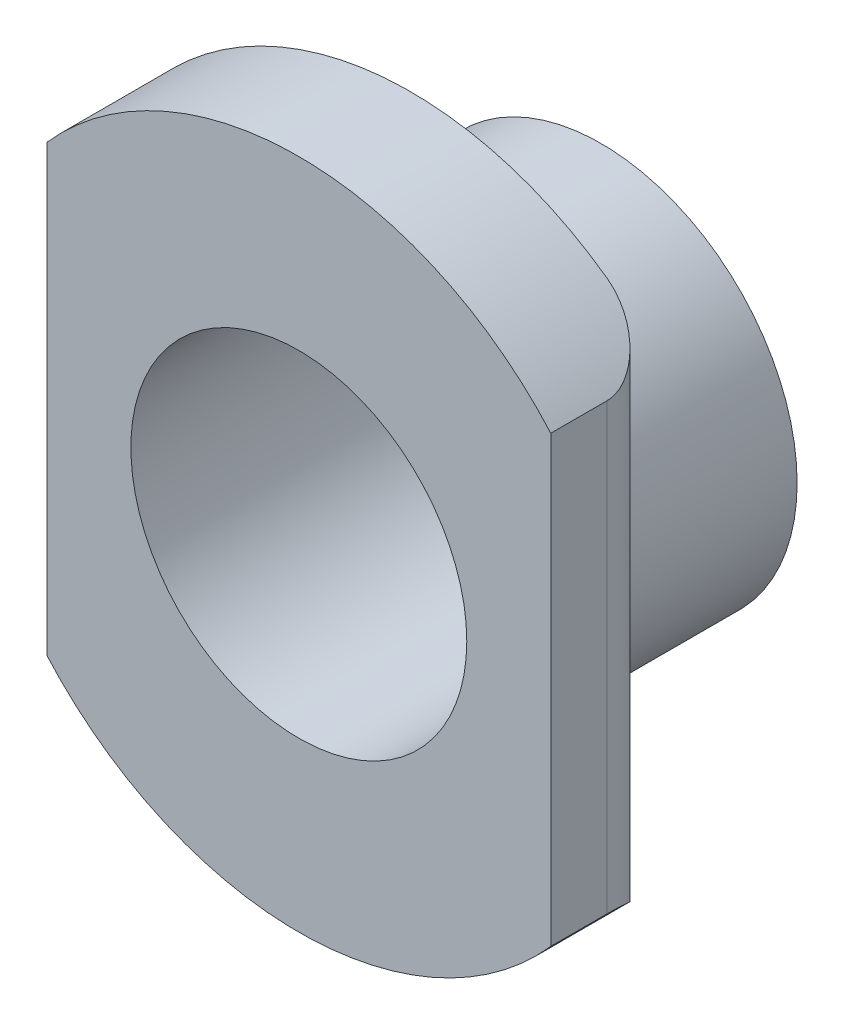
SolidWorks part; units mm, degrees
ref_plane "前视基准面" through (0, 0, 0) normal (0, 0, 1) x (1, 0, 0)
ref_plane "上视基准面" through (0, 0, 0) normal (0, 1, 0) x (1, 0, 0)
ref_plane "右视基准面" through (0, 0, 0) normal (1, 0, 0) x (0, 0, -1)
other "Configuration Table"
sketch "草图1" plane through (0, 0, 0) normal (0, 0, 1) x (1, 0, 0)
  circle A0 centre (0, 0) radius 1.75
  circle A1 centre (0, 0) radius 1.5
  dimension "D1" = 3.5
  dimension "D2" = 3
extrude "凸台-拉伸1" add sketch "草图1" along normal blind 1.7
sketch "草图2" plane through (0, 0, 1.7) normal (0, 0, 1) x (1, 0, 0)
  line L1 (-2.25, -3) -> (2.25, -3)
  line L2 (-2.25, -3) -> (-2.25, 3)
  line L3 (-2.25, 3) -> (2.25, 3)
  line L4 (2.25, -3) -> (2.25, 3)
  line L5 (-2.25, -3) -> (2.25, 3) construction
  line L6 (-2.25, 3) -> (2.25, -3) construction
  circle A0 centre (0, 0) radius 3
  circle A1 centre (0, 0) radius 1.5 construction
  circle A2 centre (0, 0) radius 1.5
  circle M6 centre (0, 0) radius 1.75
  circle M7 centre (0, 0) radius 1.5
  dimension "D1" = 6
  dimension "D2" = 4.5
extrude "凸台-拉伸2" add sketch "草图2" along normal blind 1 contours L4 A0 L2 M6 | M6 M7 region at (-1.2035, -2.666, 1.7) region at (-1.7005, 0, 1.7)
fillet "圆角1" radius 0.5 1 edges at (2.25, 0, 1.7)
